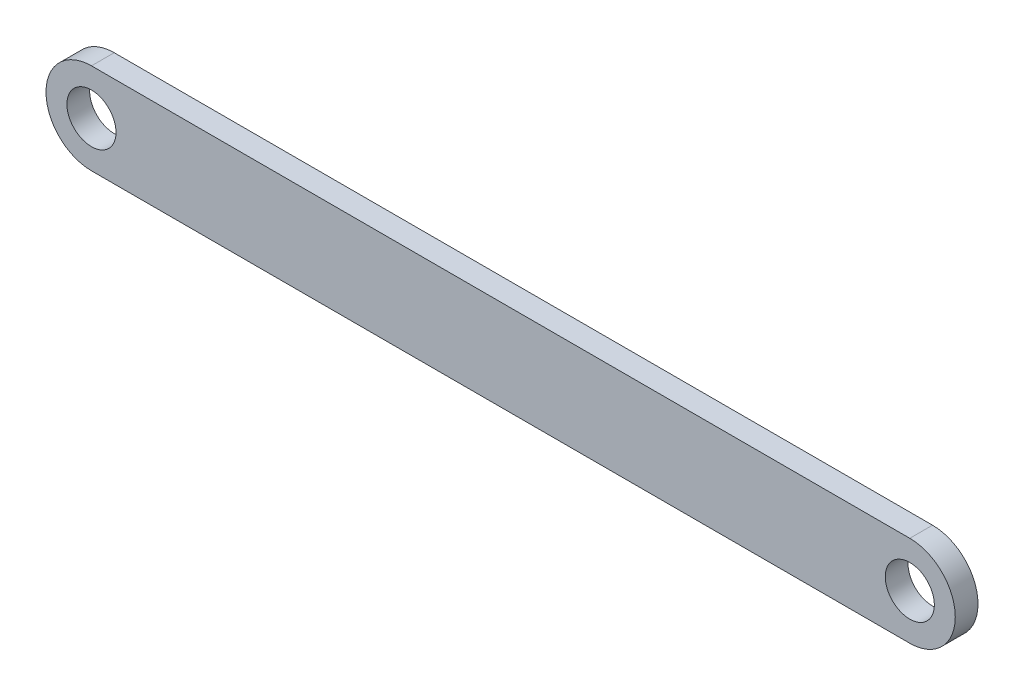
SolidWorks part; units mm, degrees
ref_plane "Front Plane" through (0, 0, 0) normal (0, 0, 1) x (1, 0, 0)
ref_plane "Top Plane" through (0, 0, 0) normal (0, 1, 0) x (1, 0, 0)
ref_plane "Right Plane" through (0, 0, 0) normal (1, 0, 0) x (0, 0, -1)
sketch "Sketch1" plane through (0, 0, 0) normal (0, 0, 1) x (1, 0, 0)
  line L1 (0, 0) -> (200, 0)
  line L2 (0, 0) -> (0, 20)
  line L3 (0, 20) -> (200, 20)
  line L4 (200, 0) -> (200, 20)
extrude "Boss-Extrude1" add sketch "Sketch1" along normal blind 5
fillet "Fillet1" 2 edges at (200, 20, 2.5) (200, 0, 2.5) type full round first side face at (100, 20, 2.5) second side face at (100, 0, 2.5) middle face at (200, 10, 2.5)
fillet "Fillet2" 2 edges at (0, 20, 2.5) (0, 0, 2.5) type full round first side face at (95, 20, 2.5) second side face at (95, 0, 2.5) middle face at (0, 10, 2.5)
sketch "Sketch2" plane through (0, 0, 5) normal (0, 0, 1) x (1, 0, 0)
  circle A0 centre (10, 10) radius 5.4
  circle A1 centre (190, 10) radius 5.4
  point P6 (0, 0)
extrude "Cut-Extrude1" cut sketch "Sketch2" against normal blind 5
